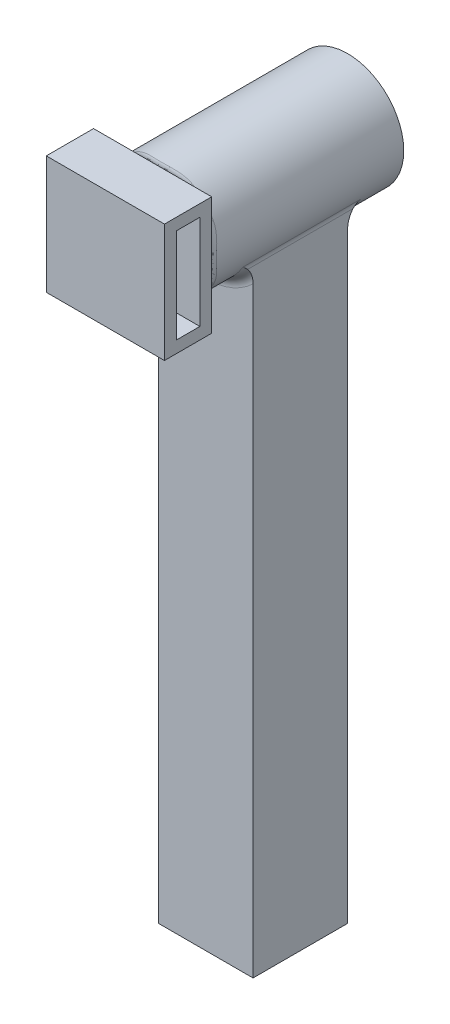
SolidWorks part; units mm, degrees
ref_plane "Front Plane" through (0, 0, 0) normal (0, 0, 1) x (1, 0, 0)
ref_plane "Top Plane" through (0, 0, 0) normal (0, 1, 0) x (1, 0, 0)
ref_plane "Right Plane" through (0, 0, 0) normal (1, 0, 0) x (0, 0, -1)
sketch "Sketch2" plane through (0, 0, 0) normal (0, 0, 1) x (1, 0, 0)
  circle A4 centre (0, 0) radius 4.75
  point P3 (25, 0)
  dimension "D1" = 9.5
ref_plane "Plane1" through (0, 0, 16.5) normal (0, 0, 1) x (1, 0, 0)
sketch "Sketch3" plane through (0, 0, 16.5) normal (0, 0, 1) x (1, 0, 0)
  line L0 (-5, 5) -> (5, 5)
  line L1 (-5, 5) -> (-5, -5)
  line L2 (-5, -5) -> (5, -5)
  line L3 (5, 5) -> (5, -5)
  circle A0 centre (0, 0) radius 4.75
  point P3 (0, 5)
  point P9 (5, 0)
  dimension "D1" = 9.5
  dimension "D2" = 10
loft "Loft1" add profiles "Sketch2", "Sketch3" connector at (0.4143, 4.7319, 0) connector at (0.1582, 4.7474, 16.5)
sketch "Sketch4" plane through (0, 0, 0) normal (0, 1, 0) x (1, 0, 0)
  line L1 (4, -12) -> (-4, -12)
  line L2 (4, -12) -> (4, -4)
  line L3 (4, -4) -> (-4, -4)
  line L4 (-4, -12) -> (-4, -4)
  line L7 (-4.75, 0) -> (-4.75, -16.5) construction
  line L8 (4.75, 0) -> (-4.75, 0) construction
  dimension "D1" = 4
  dimension "D2" = 0.75
  dimension "D3" = 8
  dimension "D4" = 8
extrude "Boss-Extrude1" add sketch "Sketch4" against normal blind 55
extrude "Boss-Extrude4" add sketch "Sketch3<7>" along normal blind 4 contours A0 L3 L0 L1 | A0 L1 L2 L3 | A0 | A0 L0 L1 | A0 L2 L3 region at (0, 4.8586, 16.5) region at (0, 0, 16.5)
sketch "Sketch3<7>" plane through (0, 0, 16.5) normal (0, 0, 1) x (1, 0, 0) same geometry as "Sketch3"
sketch "Sketch8" plane through (5, 0, 0) normal (1, 0, 0) x (0, 0, -1)
  line L0 (-20.5, 5) -> (-20.5, -5) construction
  line L1 (-19.5, 4) -> (-17.5, 4)
  line L2 (-19.5, 4) -> (-19.5, -4)
  line L3 (-19.5, -4) -> (-17.5, -4)
  line L4 (-17.5, 4) -> (-17.5, -4)
  line L5 (-20.5, 5) -> (-16.5, 5) construction
  point P4 (-19.5, 0)
  point P7 (-20.5, 0)
  point P8 (-18.5, 4)
  point P11 (-18.5, 5)
  dimension "D1" = 2
  dimension "D2" = 8
extrude "Cut-Extrude2" cut sketch "Sketch8" against normal through all both and the other way through all
fillet "Fillet1" radius 1 1 edges at (4.75, 0, 16.5)
fillet "Fillet2" radius 1 4 edges at (0, -4.75, 12) (-4, -2.5617, 8) (0, -4.75, 4) (4, -2.5617, 8)
